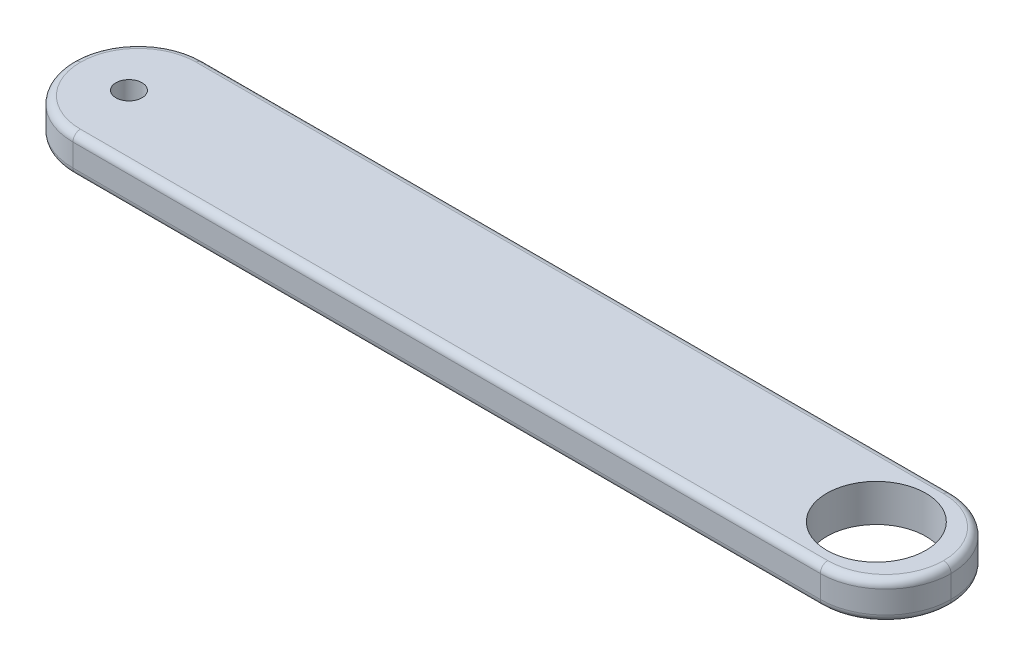
SolidWorks part; units mm, degrees
ref_plane "Alzado" through (0, 0, 0) normal (0, 0, 1) x (1, 0, 0)
ref_plane "Planta" through (0, 0, 0) normal (0, 1, 0) x (1, 0, 0)
ref_plane "Vista lateral" through (0, 0, 0) normal (1, 0, 0) x (0, 0, -1)
sketch "Croquis1" plane through (0, 0, 0) normal (0, 1, 0) x (1, 0, 0)
  line L0 (-235, 17.5) -> (0, 17.5) construction
  line L1 (0, 0) -> (-235, 0)
  line L2 (0, 0) -> (0, 35)
  line L3 (0, 35) -> (-235, 35)
  line L4 (-235, 0) -> (-235, 35)
  circle A0 centre (-20, 17.5) radius 13.25
  circle A1 centre (-220, 17.5) radius 3.5
  dimension "D2" = 26.5
  dimension "D3" = 7
  dimension "D1" = 35
  dimension "D4" = 15
  dimension "D5" = 20
  dimension "D6" = 200
extrude "Saliente-Extruir1" add sketch "Croquis1" along normal blind 10
fillet "Redondeo1" radius 17.5 4 edges at (0, 5, 0) (0, 5, -35) (-235, 5, -35) (-235, 5, 0)
fillet "Redondeo2" radius 2 12 edges at (-117.5, 0, 0) (-5.1256, 0, -5.1256) (-5.1256, 0, -29.8744) (-117.5, 0, -35) (-229.8744, 0, -29.8744) (-229.8744, 10, -5.1256) (-229.8744, 10, -29.8744) (-117.5, 10, -35) (-5.1256, 10, -29.8744) (-5.1256, 10, -5.1256) (-229.8744, 0, -5.1256) (-117.5, 10, 0)
